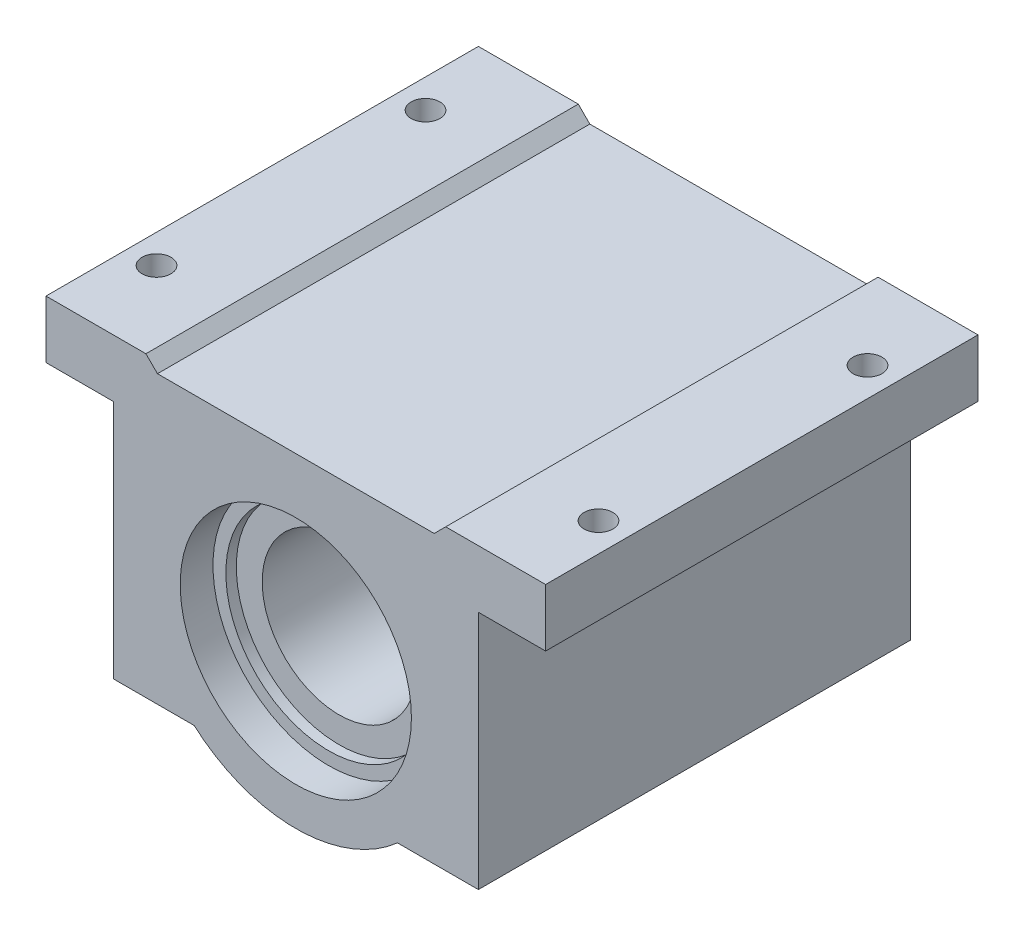
SolidWorks part; units mm, degrees
note: The reader was unsure of these and kept them because the rebuilt part matched: shared geometry of "Grooves<2>".
other "Pillow Block" parameters "D1"=31.4478, "For Shaft Dia"=25.4, "D2"=12.6007, "Supplier Grv Dia P"=42.4434, "Ht G"=30.1625, "Flange Thick H"=9.525, "Overall Wd D"=82.55, "Overall Ht F"=55.5625, "Supplier Wd G"=25.4, "D3"=16.7204, "D4"=1.4178, "D5"=41.275, "D6"=12.2773, "D7"=50.8, "Supplier Body Height K"=49.2125, "Overall Lg B"=71.4375, "Supplier Overall Wd S"=119.0625, "Outside to Outside Grooves"=228.6, "Supplier Grv Wd O"=1.7272, "Dia L"=4.7625, "Mounting Holes Center-to-Center J"=73.025, "Mounting Holes Center-to-Center K"=44.45, "Supplier F"=44.45
ref_plane "Front" through (0, 0, 0) normal (0, 0, 1) x (1, 0, 0)
ref_plane "Top" through (0, 0, 0) normal (0, 1, 0) x (1, 0, 0)
ref_plane "Right" through (0, 0, 0) normal (1, 0, 0) x (0, 0, -1)
sketch "Sketch1" plane through (0, 0, 0) normal (0, 0, 1) x (1, 0, 0)
  line L0 (-30.1625, -25.4) -> (-30.1625, 20.6375) construction
  line L1 (-30.1625, -25.4) -> (30.1625, -25.4) construction
  line L2 (-30.1625, 20.6375) -> (-41.275, 20.6375)
  line L3 (-41.275, 30.1625) -> (41.275, 30.1625) construction
  line L4 (-41.275, 20.6375) -> (-41.275, 30.1625)
  line L5 (30.1625, -25.4) -> (30.1625, 20.6375) construction
  line L6 (30.1625, 20.6375) -> (41.275, 20.6375)
  line L7 (41.275, 20.6375) -> (41.275, 30.1625)
  line L8 (0, 30.1625) -> (0, -25.4) construction
  line L9 (16.8005, -19.05) -> (30.1625, -19.05)
  line L10 (-30.1625, 20.6375) -> (-30.1625, -19.05)
  line L11 (-30.1625, -19.05) -> (-16.8005, -19.05)
  line L12 (30.1625, -19.05) -> (30.1625, 20.6375)
  line L13 (-24.765, 30.1625) -> (24.765, 30.1625) construction
  line L14 (-24.765, 30.1625) -> (-22.86, 28.2575)
  line L15 (-22.86, 28.2575) -> (22.86, 28.2575)
  line L16 (22.86, 28.2575) -> (24.765, 30.1625)
  line L17 (-24.765, 30.1625) -> (-41.275, 30.1625)
  line L18 (24.765, 30.1625) -> (41.275, 30.1625)
  circle A0 centre (0, 0) radius 12.7 construction
  circle A1 centre (0, 0) radius 19.0995
  circle A2 centre (0, 0) radius 25.4 construction
  arc A3 (-16.8005, -19.05) -> (16.8005, -19.05) centre (0, 0) ccw
  circle A4 centre (0, 0) radius 21.2217 construction
  dimension "D2" = 38.1991
  dimension "D4" = 45
  dimension "D3" = 45
  dimension "D6" = 16.51
  dimension "D1" = 1.905
extrude "Main Body" add sketch "Sketch1" along normal mid plane 71.4375
sketch "Sketch3" plane through (0, 30.1625, 0) normal (0, 1, 0) x (1, 0, 0)
  line L1 (-36.5125, -22.225) -> (36.5125, -22.225) construction
  line L2 (-36.5125, -22.225) -> (-36.5125, 22.225) construction
  line L3 (-36.5125, 22.225) -> (36.5125, 22.225) construction
  line L4 (36.5125, -22.225) -> (36.5125, 22.225) construction
  line L5 (-24.765, 35.7187) -> (-41.275, 35.7187) construction
  line L6 (-36.5125, 22.225) -> (36.5125, -22.225) construction
  line L7 (-36.5125, 22.225) -> (-36.5125, -22.225) construction
  circle A0 centre (-36.5125, 22.225) radius 2.3812
  circle A1 centre (36.5125, 22.225) radius 2.3812
  circle A2 centre (36.5125, -22.225) radius 2.3812
  circle A3 centre (-36.5125, -22.225) radius 2.3812
  point P5 (0, 0)
  dimension "D1" = 13.4937
extrude "Mounting Holes" cut sketch "Sketch3" against normal up to surface (9.525 mm away) up to face at (35.7188, 20.6375, 0)
ref_plane "Plane1" through (0, 0, 0) normal (0, 0, 1) x (1, 0, 0)
sketch "Sketch8" plane through (0, 0, 0) normal (0, 0, 1) x (1, 0, 0)
  circle A0 centre (0, 0) radius 19.0995 construction
  circle A1 centre (0, 0) radius 19.0995
  circle A2 centre (0, 0) radius 12.7 construction
  circle A3 centre (0, 0) radius 12.7
extrude "Interior" add sketch "Sketch8" along normal mid plane 57.15 separate body
sketch "Grooves" plane through (0, 0, 0) normal (1, 0, 0) x (0, 0, -1)
  line L1 (28.575, -21.2217) -> (28.575, 21.2217) construction
  line L2 (28.575, -12.7) -> (28.575, 12.7) construction
  line L4 (-28.575, 12.7) -> (-28.575, -12.7) construction
  line L5 (28.575, -16.9774) -> (28.575, -21.2217)
  line L6 (28.575, -21.2217) -> (30.3022, -21.2217)
  line L7 (30.3022, -16.9774) -> (30.3022, -21.2217)
  line L9 (-28.575, -16.9774) -> (-28.575, -21.2217)
  line L10 (-28.575, -21.2217) -> (-30.3022, -21.2217)
  line L11 (-30.3022, -16.9774) -> (-30.3022, -21.2217)
  line L13 (-30.3022, -16.9774) -> (-28.575, -16.9774)
  line L14 (28.575, -16.9774) -> (30.3022, -16.9774)
  line L15 (28.575, -16.9774) -> (28.575, 16.9774) construction
  point P13 (28.575, 0)
  dimension "Supplier Grv Dia P" = 42.4434
  dimension "D1" = 33.9547
revolve "Grooves " cut sketch "Grooves" angle 360 mid plane about axis through (0, 0, 28.575) along (0, 0, -1)
revolve "Retaining Ring" add sketch "Grooves<2>" angle 360 mid plane about axis through (0, 0, 28.575) along (0, 0, -1)
sketch "Grooves<2>" plane through (0, 0, 0) normal (1, 0, 0) x (0, 0, -1) same geometry as "Grooves"
sketch "Open Retaining Ring" [suppressed] plane through (0, 0, 0) normal (0, 0, 1) x (1, 0, 0)
  line L0 (0, 0) -> (-42.7798, -49.2125)
  line L1 (-42.7798, -49.2125) -> (42.7798, -49.2125)
  line L2 (42.7798, -49.2125) -> (0, 0)
  arc A0 (-31.149, -38.1) -> (31.149, -38.1) centre (0, 0) ccw construction
  dimension "D1" = 82
extrude "Open Retaining Ring " [suppressed] cut sketch "Open Retaining Ring" against normal mid plane 71.4375
sketch "Jog" [suppressed] plane through (0, 0, 0) normal (0, 0, 1) x (1, 0, 0)
  line L0 (57.15, -38.1) -> (-61.9125, -38.1) construction
  line L1 (-57.15, -38.1) -> (-61.9125, -38.1)
  line L2 (-61.9125, -38.1) -> (-61.9125, -19.685)
  line L3 (-61.9125, -19.685) -> (-57.15, -14.9225)
  line L4 (-57.15, 38.1) -> (-57.15, -38.1) construction
  line L5 (-57.15, -14.9225) -> (-57.15, -38.1)
  dimension "D1" = 45
  dimension "D2" = 9.8425
extrude "Jog " [suppressed] add sketch "Jog" along normal mid plane 71.4375
sketch "Slot Opening" [suppressed] plane through (0, 0, 0) normal (0, 0, 1) x (1, 0, 0)
  line L0 (0, 0) -> (0, -21.997) construction
  line L1 (-12.7, -21.997) -> (12.7, -21.997)
  line L2 (-12.7, -21.997) -> (-21.997, -38.1)
  line L3 (12.7, -21.997) -> (21.997, -38.1)
  line L4 (21.997, -38.1) -> (31.149, -38.1)
  line L5 (-31.149, -38.1) -> (-21.997, -38.1)
  line L6 (31.149, -38.1) -> (31.149, -49.2125)
  line L7 (31.149, -49.2125) -> (-31.149, -49.2125)
  line L8 (-31.149, -49.2125) -> (-31.149, -38.1)
  line L9 (-57.15, -49.2125) -> (57.15, -49.2125) construction
  circle A0 centre (0, 0) radius 25.4 construction
  dimension "D1" = 60
  dimension "Wd E" = 25.4
extrude "Slot Opening " [suppressed] cut sketch "Slot Opening" against normal through all and the other way through all
mirror "Twin Holes Mirror" [suppressed] about plane through (0, 0, 0) normal (0, 0, 1)
mirror "Twin Bodies" [suppressed] about plane through (0, 0, 0) normal (0, 0, 1)
mirror "Twin Grooves" [suppressed] about plane through (0, 0, 0) normal (0, 0, 1)
equation "\"D6@Sketch1\" = \"Overall Wd D@Sketch1\"  * .2"
equation "\"D1@Sketch1\" = \"Flange Thick H@Sketch1\" * .2"
equation "\"D1@Jog \" = \"Overall Lg B@Main Body\""
equation "\"D2@Jog\" = \"Supplier Body Height K@Sketch1\" * .2"
equation "\"Supplier Grv Dia P@Grooves\" = \"Supplier Grv Dia P@Sketch1\""
equation "\"D2@Sketch1\" = \"Supplier Grv Dia P@Sketch1\" * .9"
equation "\"D1@Grooves\" = \"Supplier Grv Dia P@Sketch1\" * .8"
equation "\"D1@Sketch3\" =  ( \"Overall Lg B@Main Body\" - \"Supplier F@Sketch3\" )  * .5"
equation "\"D1@Open Retaining Ring \" = \"Overall Lg B@Main Body\""
